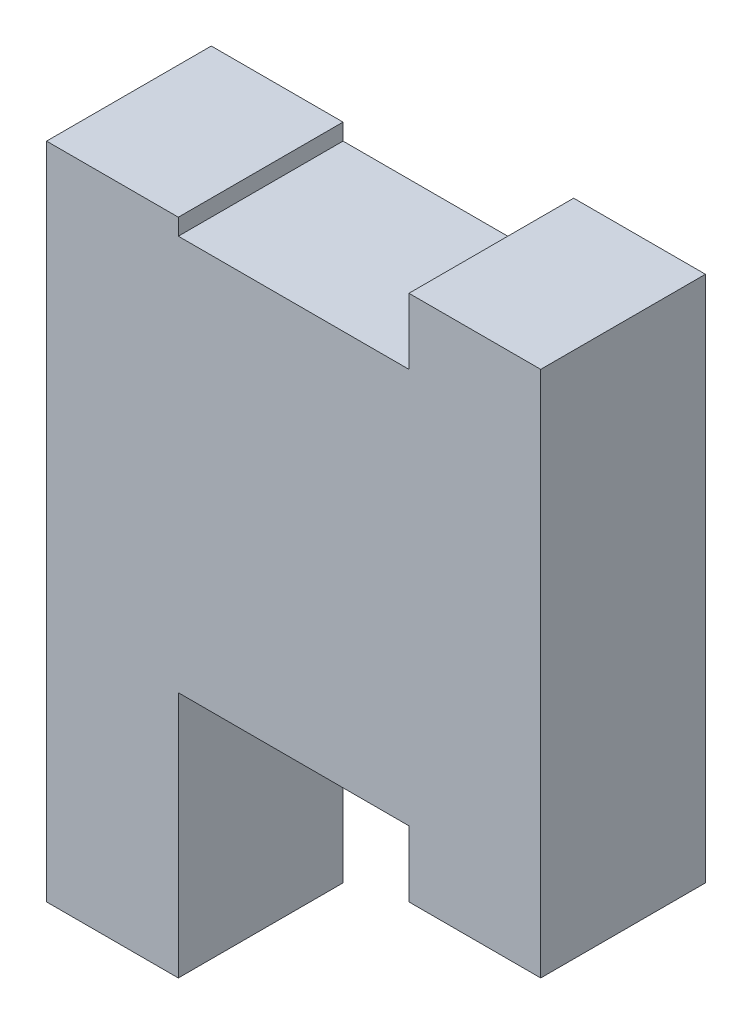
SolidWorks part; units mm, degrees
material "PBT General Purpose"
ref_plane "Front Plane" through (0, 0, 0) normal (0, 0, 1) x (1, 0, 0)
ref_plane "Top Plane" through (0, 0, 0) normal (0, 1, 0) x (1, 0, 0)
ref_plane "Right Plane" through (0, 0, 0) normal (1, 0, 0) x (0, 0, -1)
sketch "frame_outline" plane through (0, 0, 0) normal (0, 0, 1) x (1, 0, 0)
  line L110 (0, 0) -> (0, 1)
  line L111 (0, 1) -> (0.2, 1)
  line L112 (0.2, 1) -> (0.2, 0.975)
  line L113 (0.2, 0.975) -> (0.55, 0.975)
  line L114 (0.55, 0.975) -> (0.55, 1.075)
  line L115 (0.55, 1.075) -> (0.75, 1.075)
  line L116 (0.75, 1.075) -> (0.75, 0.275)
  line L117 (0.75, 0.275) -> (0.55, 0.275)
  line L118 (0.55, 0.275) -> (0.55, 0.375)
  line L119 (0.55, 0.375) -> (0.2, 0.375)
  line L120 (0.2, 0.375) -> (0.2, 0)
  line L121 (0.2, 0) -> (0, 0)
  line L122 (0.75, 0.675) -> (0.1351, 0.675) construction
  line L123 (0.55, 0.975) -> (0.55, 0.375) construction
  point P11 (0.55, 0.675)
  dimension "D1" = 1
  dimension "D2" = 0.2
  dimension "D3" = 0.35
  dimension "D4" = 0.2
  dimension "D5" = 0.6
  dimension "D6" = 0.8
  dimension "D7" = 0.325
extrude "Boss-Extrude1" add sketch "frame_outline" along normal mid plane 0.25
equation "\"t\"= 0.25'thickness of the sheets"
equation "\"t_cf\"= 0.115'thickness of single carbon fiber layer"
equation "\"t_kapton\"= 0.025'thickness of single Kapton flex layer"
equation "\"t_fr4\"= 0.1'thickness of FR4 with copper layer"
equation "\"joint_flex\"= 0.1'Width of flextures gap"
equation "\"joint_flex_eff\"= 0.02'Width of flecture after castelation"
equation "\"joint_fold\"= 0.2'Width of folding joints for 90deg fold"
equation "\"gap_tolerance\"= 0.002'Width to have interfecence fit between carbon fiber inserts"
equation "\"assemble_angle\"= 90'Angle of assembly parts"
equation "\"D1@Boss-Extrude1\"=\"t\""
equation "\"link_lift\"= 0.5'Actuation linkage amplification for the lift motion"
equation "\"link_swing\"= 0.45'Actuation linkage amplification for the swing motion"
equation "\"D7@frame_outline\"=\"link_swing\"-\"t\"/2"
